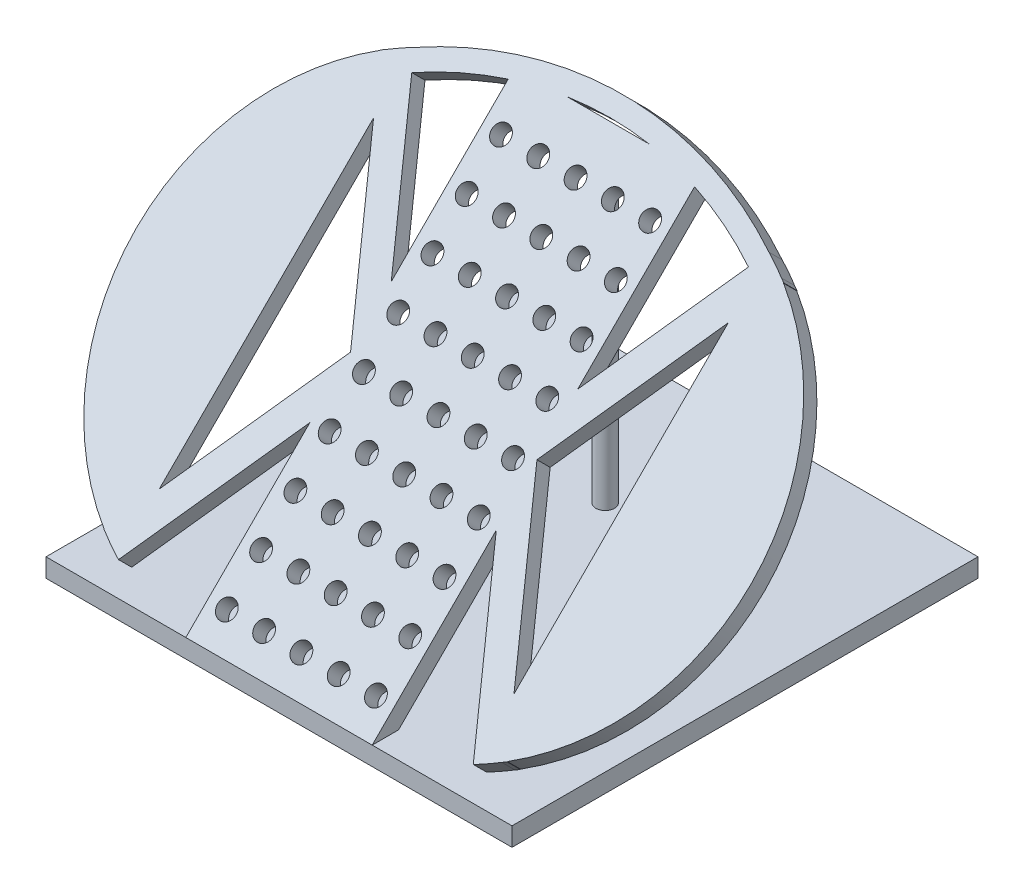
SolidWorks part; units mm, degrees
material "Hexcel AS4C (3000 Filaments)"
ref_plane "Front Plane" through (0, 0, 0) normal (0, 0, 1) x (1, 0, 0)
ref_plane "Top Plane" through (0, 0, 0) normal (0, 1, 0) x (1, 0, 0)
ref_plane "Right Plane" through (0, 0, 0) normal (1, 0, 0) x (0, 0, -1)
sketch "Sketch2" plane through (0, 0, 0) normal (0, 1, 0) x (1, 0, 0)
  line L1 (-31.75, 31.75) -> (31.75, 31.75)
  line L2 (-31.75, 31.75) -> (-31.75, -31.75)
  line L3 (-31.75, -31.75) -> (31.75, -31.75)
  line L4 (31.75, 31.75) -> (31.75, -31.75)
  line L5 (-31.75, 31.75) -> (31.75, -31.75) construction
  line L6 (-31.75, -31.75) -> (31.75, 31.75) construction
  point P0 (0, 0)
  dimension "D1" = 63.5
  dimension "D2" = 63.5
extrude "Boss-Extrude1" add sketch "Sketch2" along normal blind 2.54
ref_plane "Plane1" through (0, 17.145, 17.145) normal (0, 0.7071, 0.7071) x (1, 0, 0)
sketch "Sketch3" plane through (0, 17.145, 17.145) normal (0, 0.7071, 0.7071) x (1, 0, 0)
  line L0 (-31.75, -20.6546) -> (31.75, -20.6546) construction
  line L1 (0, -20.6546) -> (-12.7, -20.6546)
  line L2 (-12.7, -20.6546) -> (-12.7, 42.8454)
  line L5 (-12.7, 42.8454) -> (12.7, 42.8454)
  line L6 (12.7, 42.8454) -> (12.7, -20.6546)
  line L7 (12.7, -20.6546) -> (0, -20.6546)
  dimension "D1" = 12.7
  dimension "D2" = 63.5
  dimension "D3" = 25.4
extrude "Boss-Extrude2" add sketch "Sketch3" against normal blind 2.54
sketch "Sketch4" plane through (0, 17.145, 17.145) normal (0, 0.7071, 0.7071) x (1, 0, 0)
  line L0 (0, 42.8454) -> (0, 36.4954) construction
  line L1 (12.7, 42.8454) -> (-12.7, 42.8454) construction
  line L2 (-12.7, -20.6546) -> (12.7, -20.6546) construction
  circle A0 centre (0, 36.4954) radius 1.27
  circle A3 centre (-5.08, 36.4954) radius 1.27
  circle A4 centre (-10.16, 36.4954) radius 1.27
  circle A5 centre (5.08, 36.4954) radius 1.27
  circle A6 centre (10.16, 36.4954) radius 1.27
  circle A7 centre (-5.08, 36.4954) radius 1.27
  circle A8 centre (-10.16, 36.4954) radius 1.27
  circle A9 centre (0, 36.4954) radius 1.27
  circle A10 centre (5.08, 36.4954) radius 1.27
  circle A11 centre (-5.08, 29.8914) radius 1.27
  circle A12 centre (-10.16, 29.8914) radius 1.27
  circle A13 centre (0, 29.8914) radius 1.27
  circle A14 centre (5.08, 29.8914) radius 1.27
  circle A15 centre (-5.08, 23.2874) radius 1.27
  circle A16 centre (-10.16, 23.2874) radius 1.27
  circle A17 centre (0, 23.2874) radius 1.27
  circle A18 centre (5.08, 23.2874) radius 1.27
  circle A19 centre (-5.08, 16.6834) radius 1.27
  circle A20 centre (-10.16, 16.6834) radius 1.27
  circle A21 centre (0, 16.6834) radius 1.27
  circle A22 centre (5.08, 16.6834) radius 1.27
  circle A23 centre (-5.08, 10.0794) radius 1.27
  circle A24 centre (-10.16, 10.0794) radius 1.27
  circle A25 centre (0, 10.0794) radius 1.27
  circle A26 centre (5.08, 10.0794) radius 1.27
  circle A27 centre (-5.08, 3.4754) radius 1.27
  circle A28 centre (-10.16, 3.4754) radius 1.27
  circle A29 centre (0, 3.4754) radius 1.27
  circle A30 centre (5.08, 3.4754) radius 1.27
  circle A31 centre (-5.08, -3.1286) radius 1.27
  circle A32 centre (-10.16, -3.1286) radius 1.27
  circle A33 centre (0, -3.1286) radius 1.27
  circle A34 centre (5.08, -3.1286) radius 1.27
  circle A35 centre (-5.08, -9.7326) radius 1.27
  circle A36 centre (-10.16, -9.7326) radius 1.27
  circle A37 centre (0, -9.7326) radius 1.27
  circle A38 centre (5.08, -9.7326) radius 1.27
  circle A39 centre (-5.08, -16.3366) radius 1.27
  circle A40 centre (-10.16, -16.3366) radius 1.27
  circle A41 centre (0, -16.3366) radius 1.27
  circle A42 centre (5.08, -16.3366) radius 1.27
  circle A43 centre (0, 29.8914) radius 1.27
  circle A44 centre (-5.08, 29.8914) radius 1.27
  circle A45 centre (5.08, 29.8914) radius 1.27
  circle A46 centre (10.16, 29.8914) radius 1.27
  circle A47 centre (0, 23.2874) radius 1.27
  circle A48 centre (-5.08, 23.2874) radius 1.27
  circle A49 centre (5.08, 23.2874) radius 1.27
  circle A50 centre (10.16, 23.2874) radius 1.27
  circle A51 centre (0, 16.6834) radius 1.27
  circle A52 centre (-5.08, 16.6834) radius 1.27
  circle A53 centre (5.08, 16.6834) radius 1.27
  circle A54 centre (10.16, 16.6834) radius 1.27
  circle A55 centre (0, 10.0794) radius 1.27
  circle A56 centre (-5.08, 10.0794) radius 1.27
  circle A57 centre (5.08, 10.0794) radius 1.27
  circle A58 centre (10.16, 10.0794) radius 1.27
  circle A59 centre (0, 3.4754) radius 1.27
  circle A60 centre (-5.08, 3.4754) radius 1.27
  circle A61 centre (5.08, 3.4754) radius 1.27
  circle A62 centre (10.16, 3.4754) radius 1.27
  circle A63 centre (0, -3.1286) radius 1.27
  circle A64 centre (-5.08, -3.1286) radius 1.27
  circle A65 centre (5.08, -3.1286) radius 1.27
  circle A66 centre (10.16, -3.1286) radius 1.27
  circle A67 centre (0, -9.7326) radius 1.27
  circle A68 centre (-5.08, -9.7326) radius 1.27
  circle A69 centre (5.08, -9.7326) radius 1.27
  circle A70 centre (10.16, -9.7326) radius 1.27
  circle A71 centre (0, -16.3366) radius 1.27
  circle A72 centre (-5.08, -16.3366) radius 1.27
  circle A73 centre (5.08, -16.3366) radius 1.27
  circle A74 centre (10.16, -16.3366) radius 1.27
  dimension "D2" = 2.54
  dimension "D7" = 52.832
  dimension "D1" = 6.35
  dimension "D8" = 20.32
  dimension "D9" = 4.318
  dimension "D10" = 5.08
  dimension "D11" = 6.604
  dimension "D4" = 3
  dimension "D3" = 3
  dimension "D6" = 2
  dimension "D5" = 9
extrude "Cut-Extrude1" cut sketch "Sketch4" against normal blind 2.54 contours A13 | A11 | A12 | A15 | A23 | A25 | A26 | A58 | A42 | A4 | A3 | A0 | A5 | A6 | A46 | A14 | A16 | A17 | A18 | A50 | A54 | A22 | A21 | A19 | A20 | A24 | A62 | A30 | A29 | A27 | A28 | A32 | A31 | A33 | A34 | A66 | A70 | A38 | A37 | A35 | A36 | A40 | A39 | A41 | A74 region at (-5.08, 38.2814, -3.9914) region at (-10.16, 38.2814, -3.9914) region at (0, 38.2814, -3.9914) region at (-5.08, 33.6117, 0.6783) region at (-5.08, 24.2722, 10.0178) region at (0, 24.2722, 10.0178) region at (5.08, 24.2722, 10.0178) region at (5.08, 5.5933, 28.6967) region at (10.16, 24.2722, 10.0178)
sketch "Sketch5" plane through (0, 17.145, 17.145) normal (0, 0.7071, 0.7071) x (1, 0, 0)
  line L0 (12.7, 11.0954) -> (27.5024, 37.7397)
  line L1 (12.7, -20.6546) -> (12.7, 42.8454) construction
  line L2 (27.5024, 37.7397) -> (24.1719, 39.59)
  line L3 (24.1719, 39.59) -> (12.7, 18.9407)
  line L4 (12.7, 18.9407) -> (12.7, 11.0954)
  line L5 (12.7, 11.0954) -> (27.5003, -15.5501)
  line L6 (27.5003, -15.5501) -> (24.1702, -17.3998)
  line L7 (24.1702, -17.3998) -> (12.7, 3.2505)
  line L8 (12.7, 3.2505) -> (12.7, 11.0954)
  line L9 (12.7, 18.9407) -> (12.7, 3.2505)
  line M55 (12.7, -20.6546) -> (12.7, 42.8454)
  dimension "D1" = 30.48
  dimension "D2" = 3.81
  dimension "D3" = 23.622
  dimension "D4" = 150.95
  dimension "D5" = 30.48
  dimension "D6" = 23.622
extrude "Boss-Extrude3" add sketch "Sketch5" against normal blind 2.54 contours L2 L3 L0 M55 | L7 L6 L5 M55 region at (19.3037, 36.0524, -1.7624) region at (19.3028, 13.9287, 20.3613)
sketch "Sketch6" plane through (0, 17.145, 17.145) normal (0, 0.7071, 0.7071) x (1, 0, 0)
  line L0 (-12.7, 11.0954) -> (-27.5003, 37.7409)
  line L1 (-12.7, 42.8454) -> (-12.7, -20.6546) construction
  line L3 (-27.5003, 37.7409) -> (-24.1696, 39.5909)
  line L4 (-24.1696, 39.5909) -> (-12.6994, 18.9407)
  line L5 (-12.6994, 18.9407) -> (-12.7, 11.0954)
  line L6 (-12.7, 11.0954) -> (-27.5024, -15.5489)
  line L7 (-27.5024, -15.5489) -> (-24.1719, -17.3992)
  line L8 (-24.1719, -17.3992) -> (-12.7, 3.2501)
  line L9 (-12.7, 3.2501) -> (-12.7, 11.0954)
  dimension "D1" = 150.95
  dimension "D2" = 30.48
  dimension "D3" = 3.81
  dimension "D4" = 23.622
  dimension "D5" = 150.95
  dimension "D6" = 30.48
  dimension "D7" = 3.81
extrude "Boss-Extrude4" add sketch "Sketch6" against normal blind 2.54 contours L5 L4 L3 L0 | L8 L9 L6 L7 region at (-19.3025, 36.0527, -1.7627) region at (-19.3037, 13.9289, 20.3611)
sketch "Sketch7" plane through (0, 17.145, 17.145) normal (0, 0.7071, 0.7071) x (1, 0, 0)
  line L9 (27.5003, -15.5501) -> (24.1702, -17.3998) construction
  line L10 (-24.1719, -17.3992) -> (-24.1696, 39.5909)
  line L12 (24.1719, 39.59) -> (24.1719, -17.3989)
  line L13 (-24.1696, 39.5909) -> (24.1719, 39.59)
  arc A1 (24.1719, 39.59) -> (24.1719, -17.3989) centre (10.1672, 11.0956) cw
  arc A2 (-24.1696, 39.5909) -> (-24.1719, -17.3992) centre (-10.1674, 11.0953) ccw
  arc A3 (-24.1696, 39.5909) -> (24.1719, 39.59) centre (0.0003, -5.0908) cw
  dimension "D1" = 31.75
  dimension "D2" = 50.8
  dimension "D3" = 31.75
extrude "Extrude-Thin1" add sketch "Sketch7" against normal blind 2.54 thin contours A3 thin type one direction wall 2.54
extrude "Boss-Extrude10" add sketch "Sketch7<6>" against normal blind 2.54 contours L10 A2 | A1 L12 region at (-31.4727, 24.9912, 9.2988) region at (31.4733, 24.9908, 9.2992)
sketch "Sketch7<6>" plane through (0, 17.145, 17.145) normal (0, 0.7071, 0.7071) x (1, 0, 0) same geometry as "Sketch7"
sketch "Sketch8" plane through (0, 2.54, 0) normal (0, 1, 0) x (1, 0, 0)
  line L0 (0, 31.75) -> (0, 12.7) construction
  line L1 (31.75, 31.75) -> (-31.75, 31.75) construction
  circle A0 centre (0, 12.7) radius 1.27
  dimension "D2" = 2.54
  dimension "D1" = 19.05
extrude "Boss-Extrude11" add sketch "Sketch8" along normal blind 42.418 contours A0
